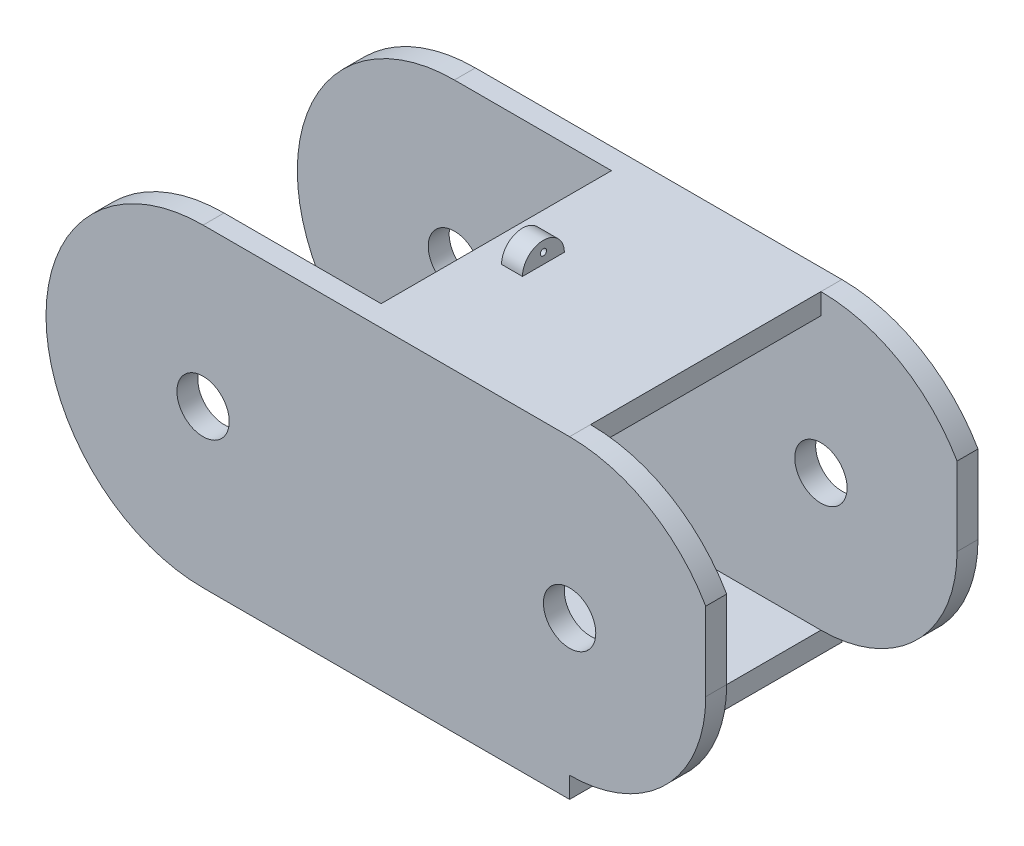
SolidWorks part; units mm, degrees
ref_plane "Front Plane" through (0, 0, 0) normal (0, 0, 1) x (1, 0, 0)
ref_plane "Top Plane" through (0, 0, 0) normal (0, 1, 0) x (1, 0, 0)
ref_plane "Right Plane" through (0, 0, 0) normal (1, 0, 0) x (0, 0, -1)
ref_plane "Right Side Plane" through (0, 0, 9.525) normal (0, 0, 1) x (1, 0, 0)
ref_plane "Inside Plane" through (0, 19.05, 0) normal (0, 1, 0) x (1, 0, 0)
sketch "Sketch1" plane through (0, 0, 0) normal (0, 1, 0) x (1, 0, 0)
  line L1 (-20.6375, 9.525) -> (20.6375, 9.525)
  line L2 (-20.6375, 9.525) -> (-20.6375, -9.525)
  line L3 (-20.6375, -9.525) -> (20.6375, -9.525)
  line L4 (20.6375, 9.525) -> (20.6375, -9.525)
  dimension "D1" = 19.05
  dimension "D2" = 41.275
  dimension "D3" = 20.6375
  dimension "D4" = 9.525
extrude "Boss-Extrude1" add sketch "Sketch1" along normal blind 19.05
sketch "Sketch2" plane through (0, 0, 9.525) normal (0, 0, 1) x (1, 0, 0)
  line L2 (-20.6375, 19.05) -> (20.6375, 19.05) construction
  line L3 (-20.6375, 19.05) -> (-20.6375, 0) construction
  line L4 (-20.6375, 0) -> (20.6375, 0) construction
  line L5 (0, 0) -> (0, 19.05) construction
  circle A0 centre (-11.1125, 9.525) radius 1.5875
  arc A1 (-11.1125, 19.05) -> (-11.1125, 0) centre (-11.1125, 9.525) ccw
  arc A2 (-11.1125, 19.05) -> (-11.1125, 0) centre (-18.9758, 9.525) ccw
  arc A3 (11.1125, 19.05) -> (11.1125, 0) centre (18.9758, 9.525) cw
  arc A4 (11.1125, 19.05) -> (11.1125, 0) centre (11.1125, 9.525) cw
  circle A5 centre (11.1125, 9.525) radius 1.5875
extrude "Cut-Extrude1" cut sketch "Sketch2" against normal blind 19.05
sketch "Sketch9" plane through (0, 19.05, 0) normal (0, 1, 0) x (1, 0, 0)
  line L1 (0, -1.27) -> (1.27, -1.27)
  line L2 (0, -1.27) -> (0, 1.27)
  line L3 (0, 1.27) -> (1.27, 1.27)
  line L4 (1.27, -1.27) -> (1.27, 1.27)
  dimension "D1" = 2.54
  dimension "D2" = 1.27
  dimension "D3" = 0
  dimension "D4" = 1.27
extrude "Boss-Extrude2" add sketch "Sketch9" along normal blind 1.27
sketch "Sketch3" plane through (0, 0, 0) normal (1, 0, 0) x (0, 0, -1)
  line L0 (-9.525, 19.05) -> (-9.525, 0) construction
  line L1 (6.985, 17.78) -> (-6.985, 17.78)
  line L2 (6.985, 17.78) -> (6.985, 1.27)
  line L3 (6.985, 1.27) -> (-6.985, 1.27)
  line L4 (-6.985, 17.78) -> (-6.985, 1.27)
  line L5 (9.525, 19.05) -> (-9.525, 19.05) construction
  line L6 (9.525, 0) -> (9.525, 19.05) construction
  line L7 (9.525, 0) -> (-9.525, 0) construction
  line L8 (-1.27, 20.32) -> (1.27, 20.32) construction
  line L9 (-1.27, 20.32) -> (-1.27, 19.05) construction
  arc A0 (-1.27, 19.05) -> (1.27, 19.05) centre (0, 19.05) cw
  circle A1 centre (0, 19.685) radius 0.1905
  arc A2 (-1.27, 19.05) -> (1.27, 19.05) centre (0, 19.726) cw
  dimension "D5" = 0.635
  dimension "D1" = 2.54
  dimension "D2" = 1.27
  dimension "D3" = 2.54
  dimension "D4" = 1.27
  dimension "D6" = 1.27
extrude "Cut-Extrude2" cut sketch "Sketch3" against normal mid plane 43.18
sketch "Sketch4" plane through (0, 19.05, 0) normal (0, 1, 0) x (1, 0, 0)
  line L0 (-11.1125, 9.525) -> (-11.1125, -9.525) construction
  line L1 (-20.6375, -9.525) -> (11.1125, -9.525)
  line L2 (-20.6375, -9.525) -> (-20.6375, -8.255)
  line L3 (-20.6375, -8.255) -> (-11.1125, -8.255)
  line L5 (11.1125, 9.525) -> (11.1125, -9.525) construction
  line L6 (-11.1125, 8.255) -> (-20.6375, 8.255)
  line L8 (-11.1125, 9.525) -> (-20.6375, 9.525)
  line L9 (-20.6375, 8.255) -> (-20.6375, 9.525)
  line L10 (20.6375, -9.525) -> (11.1125, -9.525)
  line L11 (20.6375, -9.525) -> (20.6375, -8.255)
  line L12 (20.6375, -8.255) -> (-11.1125, -8.255)
  line L14 (20.6375, 9.525) -> (11.1125, 9.525) construction
  line L15 (-11.1125, 8.255) -> (20.6375, 8.255)
  line L17 (-11.1125, 9.525) -> (20.6375, 9.525)
  line L18 (20.6375, 8.255) -> (20.6375, 9.525)
  line L20 (-11.1125, 9.525) -> (-20.6375, 9.525) construction
  line L22 (11.1125, -6.985) -> (20.6375, -6.985)
  line L23 (11.1125, -6.985) -> (11.1125, 6.985)
  line L24 (11.1125, 6.985) -> (20.6375, 6.985)
  line L25 (20.6375, -6.985) -> (20.6375, 6.985)
  point P3 (-11.4784, 8.255)
  point P12 (11.3937, -9.525)
  point P18 (-11.5208, 9.525)
  point P36 (11.1125, -8.255)
  point P37 (-10.6313, -8.255)
  dimension "D1" = 1.27
  dimension "D2" = 1.27
  dimension "D5" = 1.27
  dimension "D6" = 1.27
extrude "Cut-Extrude3" cut sketch "Sketch4" against normal blind 43.18
sketch "Sketch6" plane through (0, 0, 9.525) normal (0, 0, 1) x (1, 0, 0)
  line L1 (11.1125, 0) -> (22.2125, 0)
  line L2 (11.1125, 0) -> (11.1125, 1.27)
  line L4 (22.2125, 0) -> (22.2125, 1.27)
  line L6 (19.3675, 9.525) -> (19.3675, 17.9323)
  line L7 (19.3675, 17.9323) -> (23.6345, 11.4942)
  line L8 (23.6345, 11.4942) -> (22.2125, 1.27)
  arc A1 (19.3675, 9.525) -> (11.1125, 1.27) centre (11.1125, 9.525) cw
  dimension "D1" = 1.27
extrude "Cut-Extrude4" cut sketch "Sketch6" against normal blind 19.05
sketch "Sketch7" plane through (0, 19.05, 0) normal (0, 1, 0) x (1, 0, 0)
  line L0 (-11.1125, 8.255) -> (-11.1125, -8.255) construction
  line L1 (-15.8644, -6.985) -> (-1.5875, -6.985)
  line L2 (-15.8644, -6.985) -> (-15.8644, 6.985)
  line L3 (-15.8644, 6.985) -> (-1.5875, 6.985)
  line L4 (-1.5875, -6.985) -> (-1.5875, 6.985)
  point P5 (-5.1174, 6.704)
  point P6 (0, 0)
  dimension "D1" = 9.525
extrude "Cut-Extrude5" cut sketch "Sketch7" against normal blind 2.54
sketch "Sketch8" plane through (0, 0, 0) normal (0, 1, 0) x (1, 0, 0)
  line L0 (-11.1125, -6.985) -> (-20.6375, -6.985) construction
  line L1 (-15.875, -6.985) -> (-11.1125, -6.985)
  line L2 (-15.875, -6.985) -> (-15.875, 6.985)
  line L3 (-15.875, 6.985) -> (-11.1125, 6.985)
  line L4 (-11.1125, -6.985) -> (-11.1125, 6.985)
extrude "Cut-Extrude6" cut sketch "Sketch8" along normal blind 2.54
